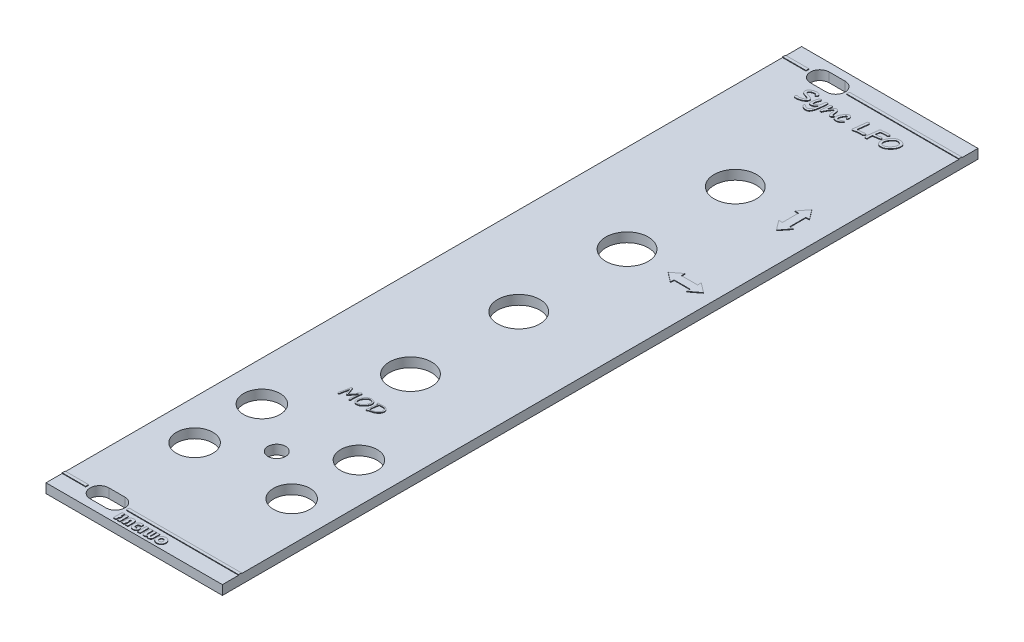
SolidWorks part; units mm, degrees
ref_plane "Ebene vorne" through (0, 0, 0) normal (0, 0, 1) x (1, 0, 0)
ref_plane "Ebene oben" through (0, 0, 0) normal (0, 1, 0) x (1, 0, 0)
ref_plane "Ebene rechts" through (0, 0, 0) normal (1, 0, 0) x (0, 0, -1)
sketch "Skizze2" plane through (0, 0, 0) normal (0, 1, 0) x (1, 0, 0)
  line L0 (-8.9, 61.25) -> (-6.2, 61.25) construction
  line L1 (-15, 64.25) -> (15, 64.25)
  line L2 (-15, 64.25) -> (-15, -64.25)
  line L3 (-15, -64.25) -> (15, -64.25)
  line L4 (15, 64.25) -> (15, -64.25)
  line L5 (0, -64.25) -> (0, 64.25) construction
  line L6 (-15, 0) -> (15, 0) construction
  line L7 (-8.9, 62.85) -> (-6.2, 62.85)
  line L8 (-8.9, 59.65) -> (-6.2, 59.65)
  line L9 (-8.9, -61.25) -> (-6.2, -61.25) construction
  line L10 (-8.9, -59.65) -> (-6.2, -59.65)
  line L11 (-8.9, -62.85) -> (-6.2, -62.85)
  circle A0 centre (-7.55, 61.25) radius 1.6 construction
  circle A1 centre (-7.55, -61.25) radius 1.6 construction
  arc A2 (-8.9, 62.85) -> (-8.9, 59.65) centre (-8.9, 61.25) ccw
  arc A3 (-6.2, 59.65) -> (-6.2, 62.85) centre (-6.2, 61.25) ccw
  arc A4 (-8.9, -59.65) -> (-8.9, -62.85) centre (-8.9, -61.25) ccw
  arc A5 (-6.2, -62.85) -> (-6.2, -59.65) centre (-6.2, -61.25) ccw
  point P10 (-7.55, 61.25)
  point P15 (-4.6, 61.25)
  point P16 (-10.5, 61.25)
  point P19 (-7.55, -61.25)
  point P24 (0, 0)
  point P92 (0, 0)
  dimension "D3" = 3.2
  dimension "D1" = 128.5
  dimension "D2" = 30
  dimension "D4" = 3
  dimension "D5" = 7.45
  dimension "D6" = 3
  dimension "D7" = 5.9
extrude "Aufsatz-Linear austragen1" add sketch "Skizze2" along normal mid plane 1.6
sketch "Skizze3" plane through (0, 0.8, 0) normal (0, 1, 0) x (1, 0, 0)
  line L0 (-15, 64.25) -> (-15, -64.25) construction
  line L1 (-15, 61.5) -> (-11, 61.5)
  line L2 (-15, 61.5) -> (-15, 61)
  line L3 (-15, 61) -> (-11, 61)
  line L4 (-11, 61.5) -> (-11, 61)
  line L5 (-13, 61) -> (-13, 61.5) construction
  line L6 (-15, 61.25) -> (-8.9, 61.25) construction
  line L7 (15, -64.25) -> (15, 64.25) construction
  line L8 (15, 61.5) -> (-4.1, 61.5)
  line L9 (15, 61.5) -> (15, 61)
  line L10 (15, 61) -> (-4.1, 61)
  line L11 (-4.1, 61.5) -> (-4.1, 61)
  line L12 (5.45, 61) -> (5.45, 61.5) construction
  line L13 (15, 61.25) -> (-4.1, 61.25) construction
  line L14 (-8.9, 61.25) -> (-4.1, 61.25) construction
  line L15 (-11, -61.25) -> (-4.1, -61.25) construction
  line L16 (-15, -61) -> (-11, -61)
  line L17 (-15, -61) -> (-15, -61.5)
  line L18 (-15, -61.5) -> (-11, -61.5)
  line L19 (-11, -61) -> (-11, -61.5)
  line L20 (-13, -61.5) -> (-13, -61) construction
  line L21 (-15, -61.25) -> (-11, -61.25) construction
  line L22 (15, -61) -> (-4.1, -61)
  line L23 (15, -61) -> (15, -61.5)
  line L24 (15, -61.5) -> (-4.1, -61.5)
  line L25 (-4.1, -61) -> (-4.1, -61.5)
  line L26 (5.45, -61.5) -> (5.45, -61) construction
  line L27 (15, -61.25) -> (-4.1, -61.25) construction
  line L28 (-15, 56.25) -> (15, 56.25) construction
  line L29 (15, 64.25) -> (-15, 64.25) construction
  line L30 (-15, -63.75) -> (15, -63.75) construction
  line L31 (-15, -64.25) -> (15, -64.25) construction
  arc A3 (-6.2, 59.65) -> (-6.2, 62.85) centre (-6.2, 61.25) ccw construction
  arc A4 (-8.9, 62.85) -> (-8.9, 59.65) centre (-8.9, 61.25) ccw construction
  arc A5 (-6.2, 59.65) -> (-6.2, 62.85) centre (-6.2, 61.25) ccw construction
  arc A6 (-8.9, 62.85) -> (-8.9, 59.65) centre (-8.9, 61.25) ccw construction
  arc A7 (-8.9, 63.35) -> (-8.9, 59.15) centre (-8.9, 61.25) ccw construction
  arc A8 (-6.2, 59.15) -> (-6.2, 63.35) centre (-6.2, 61.25) ccw construction
  arc A10 (-6.2, -62.85) -> (-6.2, -59.65) centre (-6.2, -61.25) ccw construction
  text T0 "Sync LFO" font "Segoe Print" height 2.5
  text T1 "HAGIWO" font "Bauhaus 93" height 1.5
  point P12 (-6.2, 61.25)
  point P14 (0, 0)
  point P15 (0, 0)
  point P25 (-6.2, -61.25)
  point P28 (0, 0)
  point P35 (0, 0)
  point P38 (0, 0)
  point P39 (-9.65, 61.25)
  point P40 (-11.1952, 61)
  point P51 (-8.2485, 61.25)
  point P52 (0, 0)
  point P55 (-5.4919, -61.2819)
  point P98 (5.45, 61.25)
  point P112 (-13, -61.25)
  point P128 (-13, 61.25)
  point P181 (5.45, -61.25)
  dimension "D1" = 0.5
  dimension "D2" = 0.5
  dimension "D3" = 8
  dimension "D4" = 0.5
extrude "Aufsatz-Linear austragen2" add sketch "Skizze3" along normal blind 0.1
sketch "Skizze4" plane through (0, 0.8, 0) normal (0, 1, 0) x (1, 0, 0)
  line L1 (-14.605, 50.8) -> (14.605, 50.8) construction
  line L2 (-14.605, 50.8) -> (-14.605, -50.8) construction
  line L3 (-14.605, -50.8) -> (14.605, -50.8) construction
  line L4 (14.605, 50.8) -> (14.605, -50.8) construction
  line L5 (0, -50.8) -> (0, 50.8) construction
  line L6 (-14.605, 0) -> (14.605, 0) construction
  circle A0 centre (0, 37.98) radius 3.6
  circle A1 centre (0, 19.565) radius 3.6
  circle A2 centre (0, 1.15) radius 3.6
  circle A3 centre (0, -17.265) radius 3.6
  circle A4 centre (-8.255, -34.29) radius 3.1
  circle A5 centre (8.255, -34.29) radius 3.1
  circle A6 centre (-8.255, -45.72) radius 3.1
  circle A7 centre (8.255, -45.72) radius 3.1
  circle A8 centre (0, -40.005) radius 1.5
  point P22 (0, 0)
  point P23 (0, 0)
  point P24 (0, 0)
  point P25 (0, 0)
  point P84 (0, 0)
  dimension "D3" = 6.2
  dimension "D4" = 3
  dimension "D5" = 7.2
  dimension "D1" = 29.21
  dimension "D2" = 101.6
  dimension "D6" = 12.82
  dimension "D7" = 31.235
  dimension "D8" = 49.65
  dimension "D9" = 68.065
  dimension "D10" = 85.09
  dimension "D11" = 90.805
  dimension "D12" = 96.52
  dimension "D13" = 6.35
  dimension "D14" = 22.86
extrude "Schnitt-Linear austragen1" cut sketch "Skizze4" against normal through all
sketch "Skizze5" plane through (0, 0.8, 0) normal (0, 1, 0) x (1, 0, 0)
  line L0 (0, 37.98) -> (10, 37.98) construction
  line L1 (10, 40.98) -> (10, 34.98) construction
  line L2 (10, 40.98) -> (8.75, 39.351)
  line L3 (8.75, 39.351) -> (9.375, 39.351)
  line L4 (9.375, 39.351) -> (9.375, 36.609)
  line L5 (10.625, 39.351) -> (10.625, 36.609)
  line L6 (11.25, 39.351) -> (10.625, 39.351)
  line L7 (10, 40.98) -> (11.25, 39.351)
  line L8 (11.25, 36.609) -> (10.625, 36.609)
  line L9 (8.75, 36.609) -> (9.375, 36.609)
  line L10 (10, 34.98) -> (11.25, 36.609)
  line L11 (10, 34.98) -> (8.75, 36.609)
  line L12 (0, 19.565) -> (10, 19.565) construction
  line L13 (10, 20.19) -> (10, 18.94) construction
  line L14 (7, 19.565) -> (8.629, 20.815)
  line L15 (8.629, 20.815) -> (8.629, 20.19)
  line L16 (8.629, 20.19) -> (11.371, 20.19)
  line L17 (11.371, 20.815) -> (11.371, 20.19)
  line L18 (13, 19.565) -> (11.371, 20.815)
  line L19 (13, 19.565) -> (11.371, 18.315)
  line L20 (11.371, 18.315) -> (11.371, 18.94)
  line L21 (8.629, 18.94) -> (11.371, 18.94)
  line L22 (8.629, 18.315) -> (8.629, 18.94)
  line L23 (7, 19.565) -> (8.629, 18.315)
  line L24 (0, -17.265) -> (0, -26.265) construction
  line L25 (-5, -26.265) -> (5, -26.265) construction
  line L26 (-8.255, -34.29) -> (-8.255, -41.29) construction
  line L27 (-12.255, -41.29) -> (-4.255, -41.29) construction
  line L28 (-8.255, -45.72) -> (-8.255, -52.72) construction
  line L29 (-12.255, -52.72) -> (-4.255, -52.72) construction
  text T0 "MOD" font "Segoe Print" height 2
  point P13 (10.625, 37.98)
  point P14 (9.375, 37.98)
  dimension "D1" = 75
  dimension "D2" = 1.25
  dimension "D3" = 2.5
  dimension "D4" = 75
  dimension "D5" = 6
  dimension "D6" = 7
  dimension "D7" = 9
  dimension "D8" = 10
  dimension "D9" = 7
  dimension "D10" = 8
extrude "Aufsatz-Linear austragen3" add sketch "Skizze5" along normal blind 0.1
